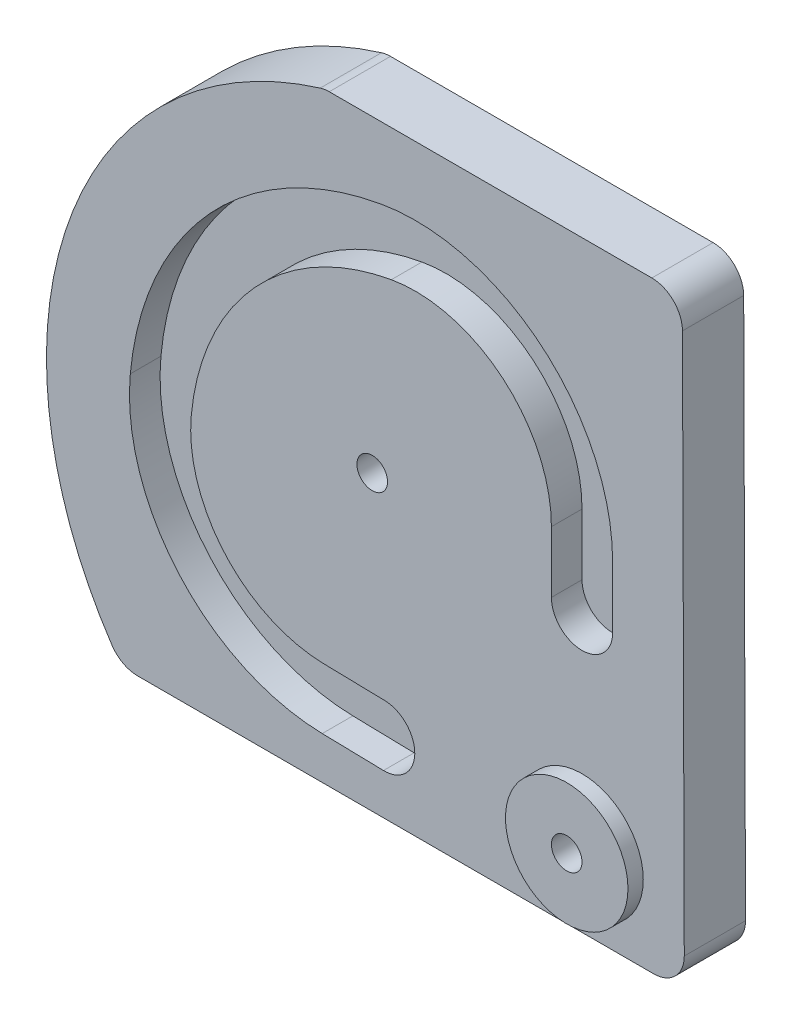
SolidWorks part; units mm, degrees
ref_plane "Front Plane" through (0, 0, 0) normal (0, 0, 1) x (1, 0, 0)
ref_plane "Top Plane" through (0, 0, 0) normal (0, 1, 0) x (1, 0, 0)
ref_plane "Right Plane" through (0, 0, 0) normal (1, 0, 0) x (0, 0, -1)
sketch "Sketch1" plane through (0, 0, 0) normal (0, 0, 1) x (1, 0, 0)
  line L0 (-32.5547, 173.4762) -> (72.8021, 173.4762)
  line L1 (-14.848, -9.6659) -> (-34.848, -9.2123)
  line L2 (-14.3946, 10.329) -> (-34.3946, 10.7826)
  line L4 (40, 66.7192) -> (40, 86.7192)
  line L5 (60, 66.7192) -> (60, 86.7192)
  line L7 (-95.1733, -23.0538) -> (73.3971, -23.0538)
  line L8 (82.802, 163.5099) -> (83.3971, -13.02)
  arc A0 (-14.848, -9.6659) -> (-14.3946, 10.329) centre (-14.6213, 0.3316) ccw
  arc A2 (40, 66.7192) -> (60, 66.7192) centre (50, 66.7192) ccw
  arc A4 (-35.4996, 173.0327) -> (-103.482, -18.6184) centre (1.826, 51.9097) ccw
  arc A5 (-97.5343, 61.1855) -> (-34.848, -9.2123) centre (-33.3874, 55.197) ccw
  arc A6 (-77.6209, 59.3265) -> (-34.3946, 10.7826) centre (-33.3874, 55.197) ccw
  circle A9 centre (50, 1.8601) radius 20
  arc A10 (-15.8148, 150.1305) -> (-97.5343, 61.1855) centre (1.826, 51.9097) ccw
  arc A11 (-12.2793, 130.4455) -> (-77.6209, 59.3265) centre (1.826, 51.9097) ccw
  circle A14 centre (-18.5146, 72.6444) radius 5
  arc A19 (-95.1733, -23.0538) -> (-103.482, -18.6184) centre (-95.1733, -13.0538) cw
  arc A20 (60, 86.7192) -> (-15.8148, 150.1305) centre (-4.4259, 86.7192) ccw
  arc A21 (40, 86.7192) -> (-12.2793, 130.4455) centre (-4.4259, 86.7192) ccw
  arc A24 (73.3971, -23.0538) -> (83.3971, -13.02) centre (73.3971, -13.0538) ccw
  circle A25 centre (50, 1.8601) radius 5
  arc A26 (82.802, 163.5099) -> (72.8021, 173.4762) centre (72.8021, 163.4762) ccw
  arc A27 (-32.5547, 173.4762) -> (-35.4996, 173.0327) centre (-32.5547, 163.4762) ccw
  point P2 (-18.5146, 0)
  point P8 (50, 65.7938)
  point P18 (-77.5607, 22.5673)
  point P26 (-61.1924, 116.9623)
  point P46 (32.2732, 127.1785)
  dimension "D2" = 10
  dimension "D3" = 10
  dimension "D4" = 10
  dimension "D5" = 20
  dimension "D6" = 20
  dimension "D7" = 20
  dimension "D8" = 10
  dimension "D10" = 79.7924
  dimension "D11" = 40
  dimension "D12" = 20
  dimension "D9" = 20
extrude "Boss-Extrude1" add sketch "Sketch1" against normal blind 10 contours L8 A24 L7 A19 A4 A27 L0 A26
extrude "Boss-Extrude2" add sketch "Sketch1<3>" along normal blind 10 contours A14 | A9 A25 | A25 | L0 A27 A4 A19 L7 A24 L8 A26 L4 A21 A11 A6 L2 A0 L1 A5 A10 A20 L5 A2 A9 A14 region at (-12.3964, 71.7045, 0) region at (30.5657, 1.8601, 0) region at (-18.5146, 72.6444, 0) region at (50, 1.8601, 0)
sketch "Sketch1<3>" plane through (0, 0, 0) normal (0, 0, 1) x (1, 0, 0) same geometry as "Sketch1"
extrude "Boss-Extrude3" add sketch "Sketch1<5>" along normal blind 15 contours A9
sketch "Sketch1<5>" plane through (0, 0, 0) normal (0, 0, 1) x (1, 0, 0) same geometry as "Sketch1"
extrude "Cut-Extrude1" cut sketch "Sketch1<6>" against normal through all both and the other way through all contours A14 | A25
sketch "Sketch1<6>" plane through (0, 0, 0) normal (0, 0, 1) x (1, 0, 0) same geometry as "Sketch1"
